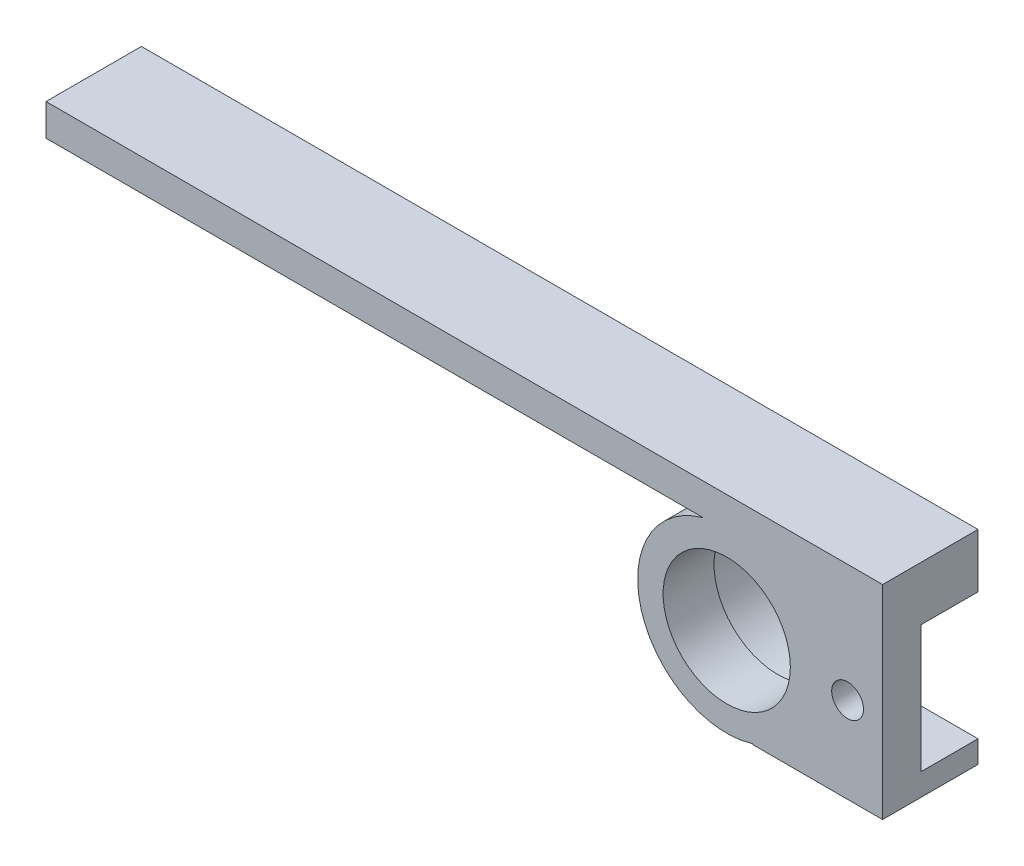
SolidWorks part; units mm, degrees
ref_plane "前视基准面" through (0, 0, 0) normal (0, 0, 1) x (1, 0, 0)
ref_plane "上视基准面" through (0, 0, 0) normal (0, 1, 0) x (1, 0, 0)
ref_plane "右视基准面" through (0, 0, 0) normal (1, 0, 0) x (0, 0, -1)
sketch "草图1" plane through (0, 0, 0) normal (0, 0, 1) x (1, 0, 0)
  line L1 (20, -10) -> (-20, -10)
  line L2 (20, -10) -> (20, 10)
  line L3 (20, 10) -> (-20, 10)
  line L4 (-20, -10) -> (-20, 10)
  line L5 (20, -10) -> (-20, 10) construction
  line L6 (20, 10) -> (-20, -10) construction
  point P0 (0, 0)
  dimension "D1" = 40
  dimension "D2" = 20
extrude "凸台-拉伸1" add sketch "草图1" along normal blind 6
sketch "草图2" plane through (0, 0, 6) normal (0, 0, 1) x (1, 0, 0)
  line L0 (20, -10) -> (20, 10) construction
  circle A0 centre (10, 0) radius 2.5
  circle A1 centre (-1, 0) radius 2.5
  circle A2 centre (-12, 0) radius 2.5
  dimension "D1" = 10
  dimension "D2" = 5
  dimension "D3" = 3
extrude "切除-拉伸1" cut sketch "草图2" against normal through all
sketch "草图3" plane through (0, 0, 6) normal (0, 0, 1) x (1, 0, 0)
  line L0 (20, 13.5) -> (20, 10)
  line L1 (20, -13.5) -> (-26.894, -13.5)
  line L3 (20, 13.5) -> (-26.894, 13.5)
  line L4 (-20, 10) -> (-20, -10)
  line L5 (-20, -10) -> (20, -10)
  line L6 (20, -10) -> (20, 10)
  line L7 (20, 10) -> (-20, 10)
  line L8 (-20, 10) -> (-20, -10)
  line L9 (-20, -10) -> (20, -10)
  line L10 (20, -10) -> (20, 10)
  line L11 (20, 10) -> (-20, 10)
  line L12 (-26.894, -13.5) -> (-26.894, 13.5)
  line L13 (20, -10.0394) -> (-26.894, 13.5) construction
  line L14 (20, 10.0394) -> (-26.894, -13.5) construction
  line L15 (20, -10) -> (20, -13.5)
  circle A0 centre (-31, 0) radius 11
  circle A1 centre (-31, 0) radius 14
  point P2 (0, 0)
  line M10 (-20, 10) -> (-20, -10)
  line M11 (-20, -10) -> (20, -10)
  line M13 (20, 10) -> (-20, 10)
  dimension "D3" = 22
  dimension "D4" = 28
  dimension "D2" = 3.5
  dimension "D1" = 0
extrude "凸台-拉伸2" add sketch "草图3" against normal blind 15 contours L3 A1 L1 L12 A0 | A1 L1 L15 M11 M10 | L1 A1 L8 A0 L12 | L8 A1 L3 L12 A0 | L8 A1 | A1 L0 L3 M10 M13 region at (-1.9449, 11.7771, 6) region at (-1.9449, -11.7771, 6) region at (-23.0173, 9.0328, 6) region at (-27.2274, 11.7946, 6) region at (-18.7882, 0, 6) region at (-23.0173, -9.0328, 6)
sketch "草图5" plane through (0, 0, 6) normal (0, 0, 1) x (1, 0, 0)
  circle A0 centre (-31, 0) radius 10
  circle A1 centre (-31, 0) radius 11 construction
  circle A2 centre (-31, 0) radius 11
  dimension "D1" = 20
extrude "凸台-拉伸3" add sketch "草图5" against normal blind 8
sketch "草图6" plane through (0, 0, 6) normal (0, 0, 1) x (1, 0, 0)
  circle A0 centre (-31, 0) radius 8.5
  circle A1 centre (-31, 0) radius 10 construction
  circle A2 centre (-31, 0) radius 10
  dimension "D1" = 17
sketch "草图7" plane through (0, 13.5, 0) normal (0, 1, 0) x (1, 0, 0)
  circle A0 centre (-17.1666, 1.953) radius 2.6594
sketch "草图8" plane through (20, 0, 0) normal (1, 0, 0) x (0, 0, -1)
  line L1 (-6, 13.5) -> (9, 13.5)
  line L2 (-6, 13.5) -> (-6, 18.5)
  line L3 (-6, 18.5) -> (9, 18.5)
  line L4 (9, 13.5) -> (9, 18.5)
  dimension "D1" = 5
extrude "凸台-拉伸4" add sketch "草图8" against normal blind 500
sketch "草图9" plane through (0, 0, -9) normal (0, 0, -1) x (-1, 0, 0)
  line L1 (24.4567, 15.8334) -> (28.494, 15.8334)
  line L2 (24.4567, 15.8334) -> (24.4567, 12.469)
  line L3 (24.4567, 12.469) -> (28.494, 12.469)
  line L4 (28.494, 15.8334) -> (28.494, 12.469)
extrude "凸台-拉伸5" add sketch "草图9" against normal through all
sketch "草图10" plane through (0, 0, 6) normal (0, 0, 1) x (1, 0, 0)
  line L0 (-12, 0) -> (-1, 0) construction
  line L1 (-6.5, 0) -> (-6.5, 18.5) construction
  line L2 (-480, 18.5) -> (20, 18.5) construction
  line L4 (-6.5, 18.5) -> (20, 18.5)
  line L5 (-6.5, 18.5) -> (-6.5, -13.5)
  line L6 (-6.5, -13.5) -> (20, -13.5)
  line L7 (20, 18.5) -> (20, -13.5)
extrude "切除-拉伸2" cut sketch "草图10" against normal through all
sketch "草图11" plane through (0, 18.5, 0) normal (0, 1, 0) x (1, 0, 0)
  line L0 (-138.0156, 9) -> (-138.0156, -6.0139)
  line L1 (-480, 9) -> (-6.5, 9) construction
  line L2 (-138.0156, 350.7091) -> (-138.0156, -19.2909) construction
sketch "草图12" plane through (0, 18.5, 0) normal (0, 1, 0) x (1, 0, 0)
  line L1 (-138.0156, -6.0139) -> (-501.7351, -6.0139)
  line L2 (-138.0156, -6.0139) -> (-138.0156, 21.5219)
  line L3 (-138.0156, 21.5219) -> (-501.7351, 21.5219)
  line L4 (-501.7351, -6.0139) -> (-501.7351, 21.5219)
extrude "切除-拉伸3" cut sketch "草图12" against normal through all
